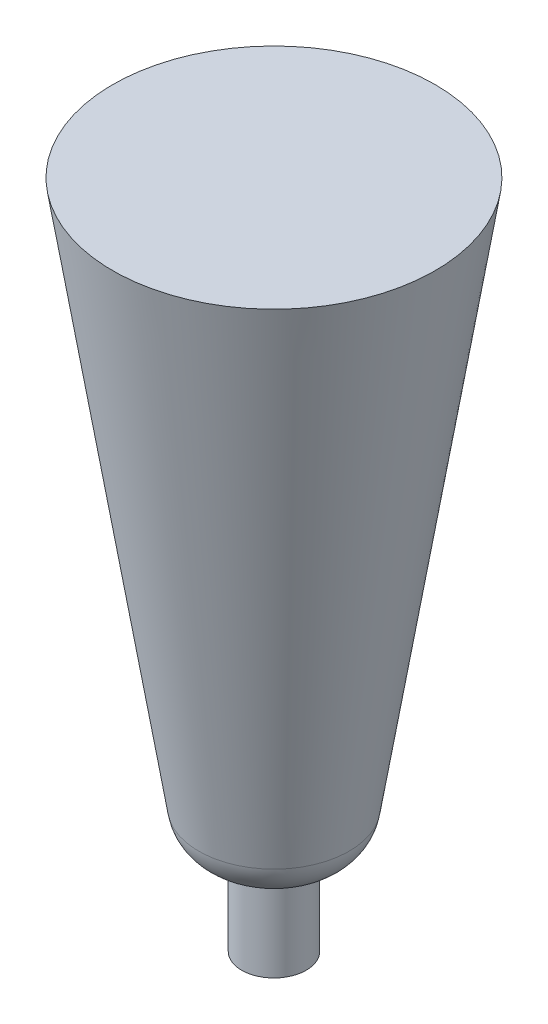
SolidWorks part; units mm, degrees
ref_plane "Front Plane" through (0, 0, 0) normal (0, 0, 1) x (1, 0, 0)
ref_plane "Top Plane" through (0, 0, 0) normal (0, 1, 0) x (1, 0, 0)
ref_plane "Right Plane" through (0, 0, 0) normal (1, 0, 0) x (0, 0, -1)
sketch "Sketch2" plane through (0, 0, 0) normal (0, 0, 1) x (1, 0, 0)
  line L0 (0, 0) -> (0, 83.5535) construction
  line L1 (0, 0) -> (3.81, 0)
  line L2 (3.81, 0) -> (3.81, 10.16)
  line L16 (8.8674, 14.6804) -> (9.1362, 16.3866)
  line L17 (9.1362, 16.3866) -> (19, 79)
  line L21 (0, 79) -> (19, 79)
  line L24 (0, 0) -> (0, 79)
  arc A1 (3.81, 10.16) -> (8.8674, 14.6804) centre (3.5729, 15.5145) ccw
  point P2 (41.6211, 66.7911)
  point P8 (0, 0)
  point P10 (25.0125, 15.3594)
  point P11 (22.0162, 15.243)
  point P12 (0, 0)
  point P14 (25.0125, 25.1108)
  point P15 (25.0125, 25.5888)
  point P16 (28.2045, 26.3573)
  point P18 (41.4225, 79)
  point P19 (0, 0)
  point P20 (0, 0)
  point P21 (0, 0)
  point P22 (0, 0)
  point P23 (28.8945, 27.3437)
  point P24 (0, 0)
  point P25 (26.6617, 16.1801)
  point P26 (0, 0)
  point P27 (27.6541, 19.4051)
  point P28 (14.5766, 11.4676)
  point P29 (20.5952, 20.0623)
  point P30 (15.4307, 14.6353)
  point P31 (10.9441, 14.2011)
  point P32 (0, 0)
  point P33 (10.713, 14.1374)
  point P34 (10.7282, 14.2556)
  point P35 (10.9161, 17.2566)
  point P36 (10.3171, 16.206)
  point P37 (8.8674, 14.6804)
  dimension "D3" = 19
  dimension "D1" = 3.81
  dimension "D2" = 10.16
  dimension "D4" = 79
revolve "Revolve6" add sketch "Sketch2" angle 360 about L0
